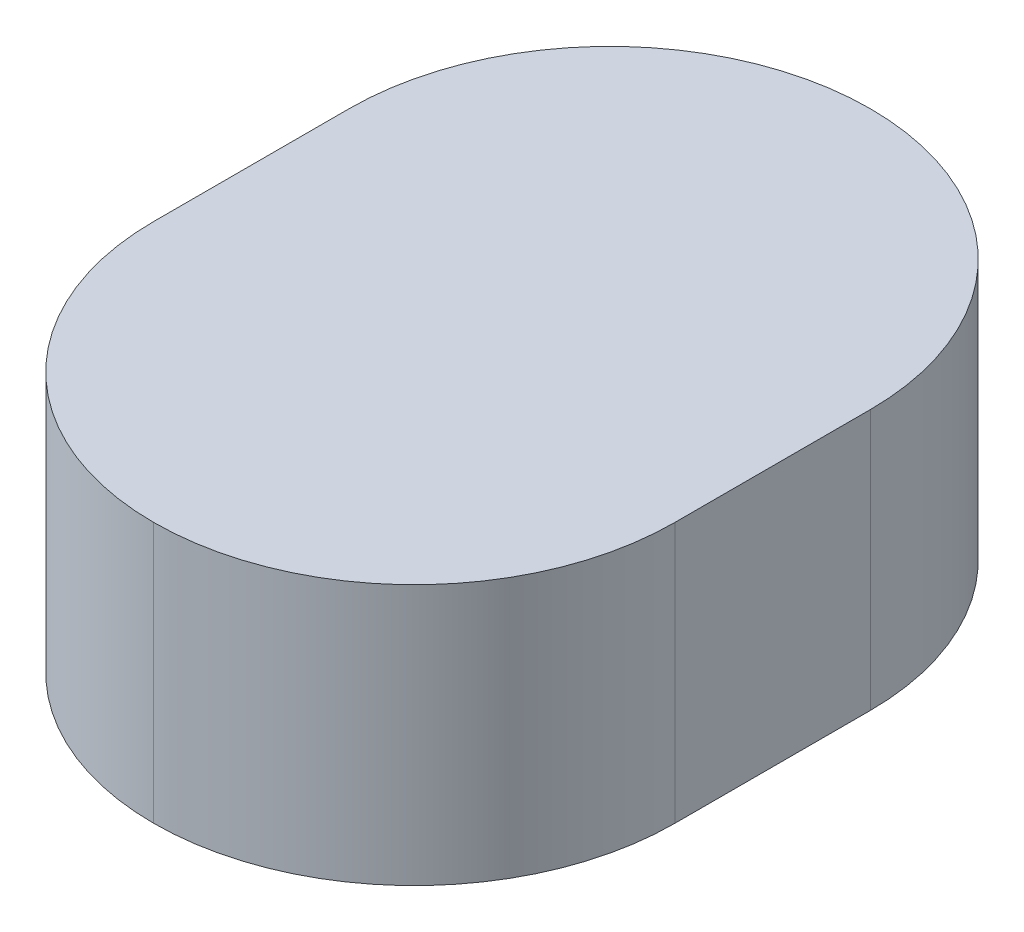
SolidWorks part; units mm, degrees
ref_plane "Front Plane" through (0, 0, 0) normal (0, 0, 1) x (1, 0, 0)
ref_plane "Top Plane" through (0, 0, 0) normal (0, 1, 0) x (1, 0, 0)
ref_plane "Right Plane" through (0, 0, 0) normal (1, 0, 0) x (0, 0, -1)
sketch "Sketch1" plane through (0, 0, 0) normal (0, 1, 0) x (1, 0, 0)
  line L0 (0, 0) -> (40, 0)
  line L1 (40, 0) -> (40, 55)
  line L2 (40, 55) -> (0, 55)
  line L4 (0, 55) -> (0, 0)
  dimension "D1" = 55
  dimension "D2" = 40
extrude "Boss-Extrude1" add sketch "Sketch1" along normal blind 20
fillet "Fillet1" radius 20 4 edges at (0, 10, 0) (0, 10, -55) (40, 10, 0) (40, 10, -55)
